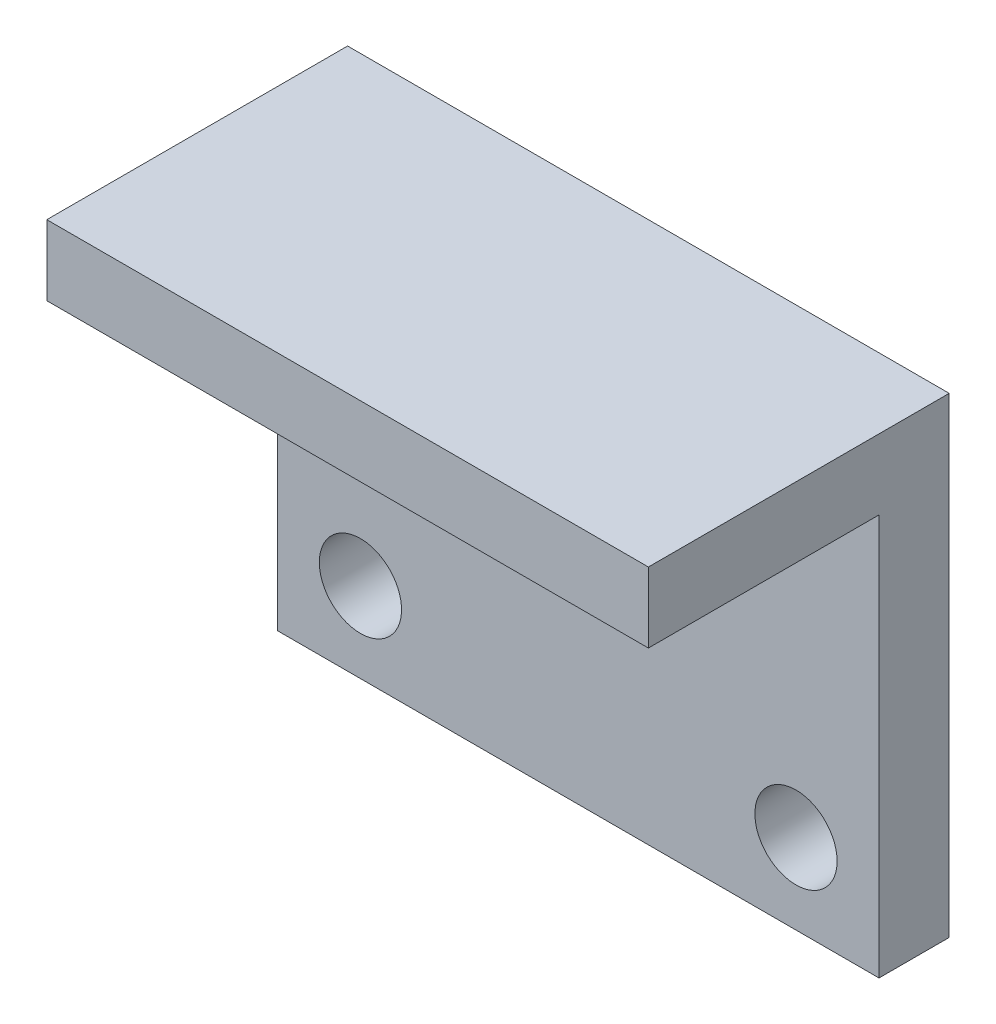
SolidWorks part; units mm, degrees
ref_plane "Front Plane" through (0, 0, 0) normal (0, 0, 1) x (1, 0, 0)
ref_plane "Top Plane" through (0, 0, 0) normal (0, 1, 0) x (1, 0, 0)
ref_plane "Right Plane" through (0, 0, 0) normal (1, 0, 0) x (0, 0, -1)
sketch "Sketch4" plane through (0, 0, 0) normal (0, 0, 1) x (1, 0, 0)
  line L0 (0, -15.2143) -> (0, 15.3214) construction
  line L1 (-15, 10) -> (15, 10)
  line L2 (-15, 10) -> (-15, -10)
  line L3 (-15, -10) -> (15, -10)
  line L4 (15, 10) -> (15, -10)
  circle A0 centre (10.86, -6) radius 2.05
  circle A1 centre (-10.86, -6) radius 2.05
  point P0 (0, 0)
  dimension "D3" = 4.1
  dimension "D4" = 4.14
  dimension "D5" = 4
  dimension "D1" = 30
  dimension "D2" = 20
extrude "Boss-Extrude2" add sketch "Sketch4" along normal blind 3.5
sketch "Sketch5" plane through (0, 0, 0) normal (0, 0, 1) x (1, 0, 0)
  line L0 (15, 10) -> (15, 13.5)
  line L1 (15, 10) -> (-15, 10)
  line L2 (-15, 10) -> (-15, 13.5)
  line L3 (-15, 13.5) -> (15, 13.5)
  dimension "D1" = 3.5
extrude "Boss-Extrude3" add sketch "Sketch5" along normal blind 15
